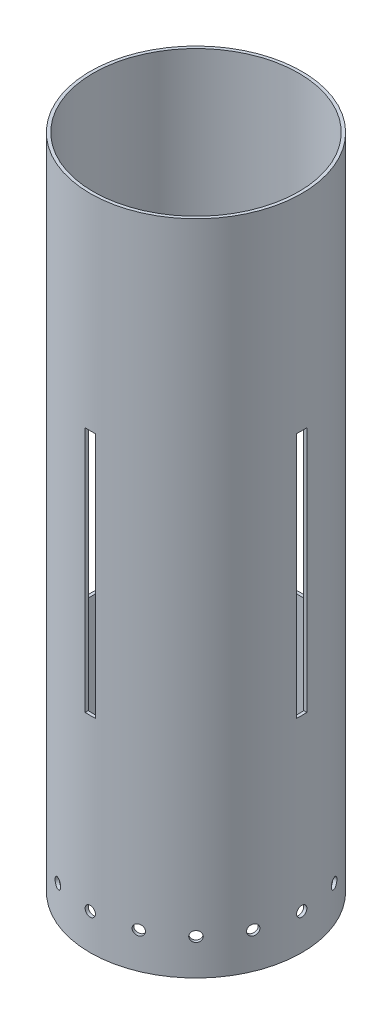
SolidWorks part; units mm, degrees
ref_plane "Front Plane" through (0, 0, 0) normal (0, 0, 1) x (1, 0, 0)
ref_plane "Top Plane" through (0, 0, 0) normal (0, 1, 0) x (1, 0, 0)
ref_plane "Right Plane" through (0, 0, 0) normal (1, 0, 0) x (0, 0, -1)
sketch "Sketch1" plane through (0, 0, 0) normal (0, 1, 0) x (1, 0, 0)
  circle A0 centre (0, 0) radius 63.5
  circle A1 centre (0, 0) radius 65.405
  dimension "D1" = 127
  dimension "D2" = 130.81
extrude "Boss-Extrude1" add sketch "Sketch1" against normal blind 406.4
ref_plane "Plane1" through (0, 0, 65.405) normal (0, 0, 1) x (1, 0, 0)
ref_axis "Axis1" through (0, -406.4, 0) along (0, 1, 0)
sketch "Sketch2" plane through (0, 0, 65.405) normal (0, 0, 1) x (1, 0, 0)
  line L1 (-3.175, -127) -> (3.175, -127)
  line L2 (-3.175, -127) -> (-3.175, -279.4)
  line L3 (-3.175, -279.4) -> (3.175, -279.4)
  line L4 (3.175, -127) -> (3.175, -279.4)
  line L5 (65.405, 0) -> (-65.405, 0) construction
  point P4 (0, -279.4)
  dimension "D1" = 6.35
  dimension "D2" = 152.4
  dimension "D3" = 127
extrude "Cut-Extrude2" cut sketch "Sketch2" against normal blind 2.54
pattern_circular "CirPattern1" count 4 over 360 about axis through (0, -406.4, 0) along (0, 1, 0) of "Cut-Extrude2"
sketch "Sketch4" plane through (0, 0, 65.405) normal (0, 0, 1) x (1, 0, 0)
  line L0 (3.175, -279.4) -> (-3.175, -279.4) construction
  line L2 (-65.405, -406.4) -> (65.405, -406.4) construction
  circle A0 centre (0, -384.175) radius 3.175
  point P0 (0, -384.175)
  point P3 (0, -279.4)
  dimension "D2" = 6.35
  dimension "D1" = 22.225
extrude "Cut-Extrude3" cut sketch "Sketch4" against normal up to next
pattern_circular "CirPattern2" count 16 over 360 about axis through (0, -406.4, 0) along (0, 1, 0) of "Cut-Extrude3"
equation "\"Slot Width\"= 0.25in"
equation "\"Slot Length\"= 6in"
equation "\"D1@Sketch2\"=\"Slot Width\""
equation "\"D2@Sketch2\"=\"Slot Length\""
